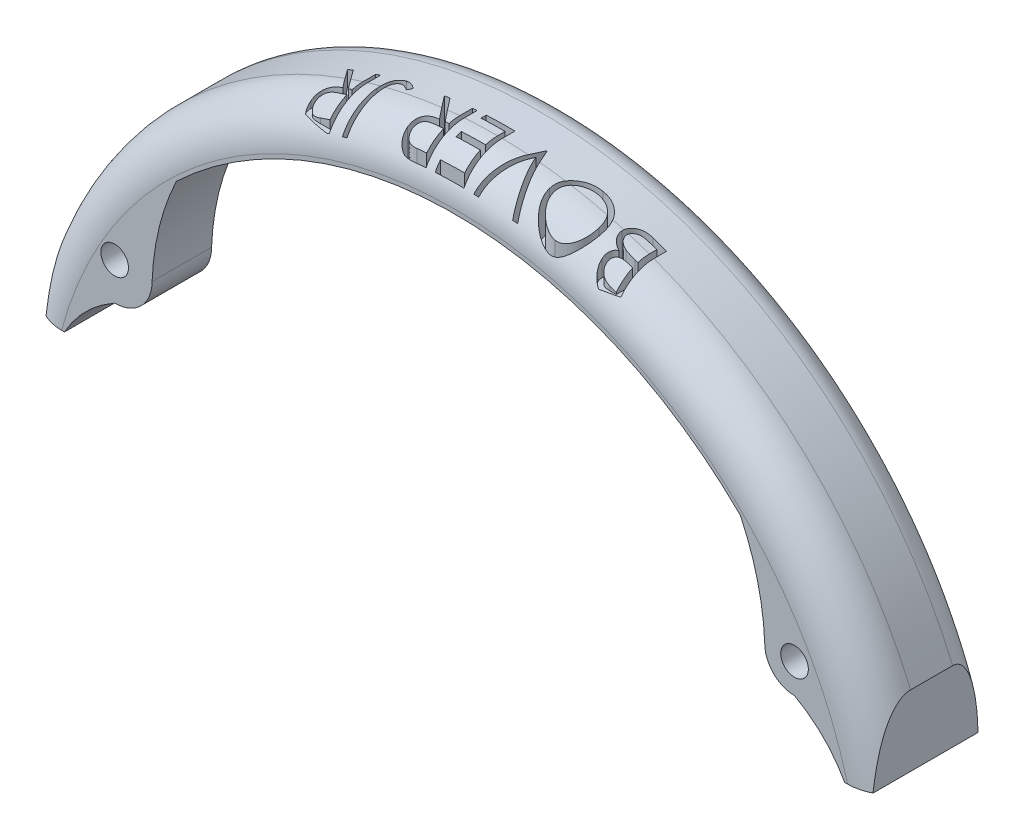
SolidWorks part; units mm, degrees
ref_plane "Alzado" through (0, 0, 0) normal (0, 0, 1) x (1, 0, 0)
ref_plane "Planta" through (0, 0, 0) normal (0, 1, 0) x (1, 0, 0)
ref_plane "Vista lateral" through (0, 0, 0) normal (1, 0, 0) x (0, 0, -1)
sketch "Croquis1" plane through (0, 0, 0) normal (0, 0, 1) x (1, 0, 0)
  line L0 (189.145, -62.21) -> (189.145, -59.4) construction
  line L1 (189.145, -59.4) -> (190, -59.4) construction
  line L2 (190, -59.4) -> (190, -61.4) construction
  line L16 (190, -61.4) -> (103.5134, -61.4) construction
  line L17 (103.3464, -61.8156) -> (103.874, -60.5025) construction
  line L18 (150, -29.805) -> (150, -32.305) construction
  line L19 (201.4085, -67.29) -> (195.9085, -67.29)
  line L20 (149.2925, -29.805) -> (150.7075, -29.805) construction
  line L21 (150, -29.805) -> (150, -26.805) construction
  line L23 (103.5134, -61.4) -> (100.5134, -61.4) construction
  line L24 (201.4085, -67.29) -> (195.9085, -67.29) construction
  line L25 (104.0915, -67.29) -> (98.5915, -67.29)
  line L26 (198.3866, -67.2011) -> (198.7238, -68.5754) construction
  line L27 (198.4085, -67.29) -> (201.4085, -67.29) construction
  line L28 (101.2762, -68.5754) -> (101.6134, -67.2011) construction
  line L29 (101.5915, -67.29) -> (98.5915, -67.29) construction
  line L30 (190, -61.4) -> (190, -67.29) construction
  line L31 (201.4085, -26.805) -> (98.5915, -26.805) construction
  line L32 (101.5915, -67.29) -> (104.0915, -67.29) construction
  line L33 (190, -67.29) -> (195.9085, -67.29) construction
  line L34 (186.5, -57.9) -> (183.643, -57.9) construction
  line L35 (150, -32.305) -> (159.1486, -32.305) construction
  line L36 (159.1486, -32.305) -> (139.6047, -32.305) construction
  line L37 (183.643, -57.9) -> (183.643, -46.2258) construction
  line L38 (114.4, -57) -> (117.257, -57) construction
  line L39 (117.257, -57) -> (117.257, -45.3505) construction
  circle A1 centre (190, -57.9) radius 1.5 construction
  arc A2 (201.4085, -67.29) -> (98.5915, -67.29) centre (150, -79.6871) ccw
  arc A3 (186.5, -57.9) -> (190, -61.4) centre (190, -57.9) ccw
  arc A4 (110, -61.4) -> (114.4, -57) centre (110, -57) ccw
  arc A6 (190, -61.4) -> (195.9085, -67.29) centre (182.782, -74.5491) cw
  arc A7 (110, -61.4) -> (104.0915, -67.29) centre (117.218, -74.5491) ccw
  arc A8 (186.5, -57.9) -> (183.643, -46.2258) centre (156.522, -59.0496) ccw
  arc A9 (114.4, -57) -> (117.257, -45.3505) centre (144.3769, -58.1766) cw
  arc A10 (183.643, -46.2258) -> (117.257, -45.3505) centre (150, -79.9188) ccw
  circle A11 centre (110, -57) radius 1.625
  circle A12 centre (190, -57.9) radius 1.625
  dimension "D1" = 8.8
  dimension "D2" = 98.5915
  dimension "D3" = 52.8821
  dimension "D4" = 15
  dimension "D5" = 30
  dimension "D6" = 47.6138
  dimension "D9" = 42.6163
  dimension "D10" = 3.25
  dimension "D7" = 117.257
  dimension "D8" = 41.0131
extrude "Saliente-Extruir1" add sketch "Croquis1" along normal blind 7
sketch "Croquis7" plane through (0, 0, 7) normal (0, 0, 1) x (1, 0, 0)
  line L0 (98.5915, -67.29) -> (101.3415, -67.29) construction
  line L1 (98.5915, -67.29) -> (104.0915, -67.29) construction
  line L2 (101.3415, -67.29) -> (101.3415, -58.9779) construction
  line L3 (201.4085, -67.29) -> (198.6585, -67.29) construction
  line L4 (98.5915, -67.29) -> (101.3415, -67.29)
  line L7 (101.3415, -67.29) -> (101.3415, -58.9779)
  line L8 (195.9085, -67.29) -> (201.4085, -67.29) construction
  line L9 (198.6585, -67.29) -> (198.6585, -58.9779) construction
  line L10 (198.6585, -58.9779) -> (198.6585, -67.29)
  line L11 (198.6585, -67.29) -> (201.4085, -67.29)
  arc A0 (201.4085, -67.29) -> (98.5915, -67.29) centre (150, -79.6871) ccw construction
  arc A1 (98.5915, -67.29) -> (101.3415, -58.9779) centre (150, -79.6871) cw
  arc A2 (198.6585, -58.9779) -> (201.4085, -67.29) centre (150, -79.6871) cw
extrude "Cortar-Extruir4" cut sketch "Croquis7" against normal up to vertex (7 mm away) up to point (98.5915, -67.29, 0)
fillet "Redondeo28" radius 5 1 edges at (150, -26.805, 7)
sketch "Croquis15" plane through (0, 0, 0) normal (0, 0, -1) x (-1, 0, 0)
  line L0 (-198.6585, -67.29) -> (-198.4085, -67.29)
  line L1 (-195.9085, -67.29) -> (-198.6585, -67.29) construction
  line L2 (-198.3866, -67.2011) -> (-198.7238, -68.5754) construction
  line L3 (-198.6585, -67.29) -> (-198.6585, -58.9779)
  line L4 (-101.3415, -67.29) -> (-101.5915, -67.29)
  line L5 (-101.3415, -67.29) -> (-104.0915, -67.29) construction
  line L6 (-101.2762, -68.5754) -> (-101.6134, -67.2011) construction
  line L7 (-101.3415, -67.29) -> (-101.3415, -58.9779)
  line L8 (-198.6585, -58.9779) -> (-198.6585, -67.29) construction
  arc A0 (-198.4085, -67.29) -> (-101.5915, -67.29) centre (-150, -79.8051) cw
  arc A1 (-198.6585, -58.9779) -> (-101.3415, -58.9779) centre (-150, -79.6871) cw
  dimension "D1" = 50.0001
  dimension "D2" = 52.8821
extrude "Saliente-Extruir7" add sketch "Croquis15" along normal blind 5.95
fillet "Redondeo29" radius 3 1 edges at (150, -26.805, -5.95)
sketch "Croquis18" plane through (0, 0, 7) normal (0, 0, 1) x (1, 0, 0)
  line L0 (150, -129.775) -> (150, -26.805) construction
  line L1 (180, -129.8) -> (120, -129.75) construction
  line L2 (103.7506, -67.29) -> (104.0915, -67.29) construction
  line L3 (150, -26.805) -> (146.6124, -26.805)
  line L4 (150, -26.805) -> (150, -23.3665)
  line L5 (150, -23.3665) -> (146.6124, -23.3665)
  line L6 (146.6124, -26.805) -> (146.6124, -23.3665)
  arc A0 (198.6585, -58.9779) -> (101.3415, -58.9779) centre (150, -79.6871) ccw construction
  dimension "D1" = 42.8618
  dimension "D2" = 43.9235
extrude "Saliente-Extruir9" add sketch "Croquis18" against normal up to vertex separate body
sketch "Croquis19" plane through (0, -23.3665, 0) normal (0, 1, 0) x (1, 0, 0)
  line L0 (148.3062, -7) -> (148.3062, -0.5) construction
  line L2 (194.6054, -0.5) -> (110.4039, -0.5) construction
  text T0 "           BOVER JR" font "Century Gothic" height 6
extrude "Cortar-Extruir12" cut sketch "Croquis19" against normal blind 8.75
sketch "Croquis20" plane through (0, 0, 7) normal (0, 0, 1) x (1, 0, 0)
  line L1 (146.6124, -26.805) -> (150, -26.805)
  line L2 (146.6124, -26.805) -> (146.6124, -23.3665)
  line L3 (146.6124, -23.3665) -> (150, -23.3665)
  line L4 (150, -26.805) -> (150, -23.3665)
extrude "Cortar-Extruir13" cut sketch "Croquis20" against normal up to vertex
